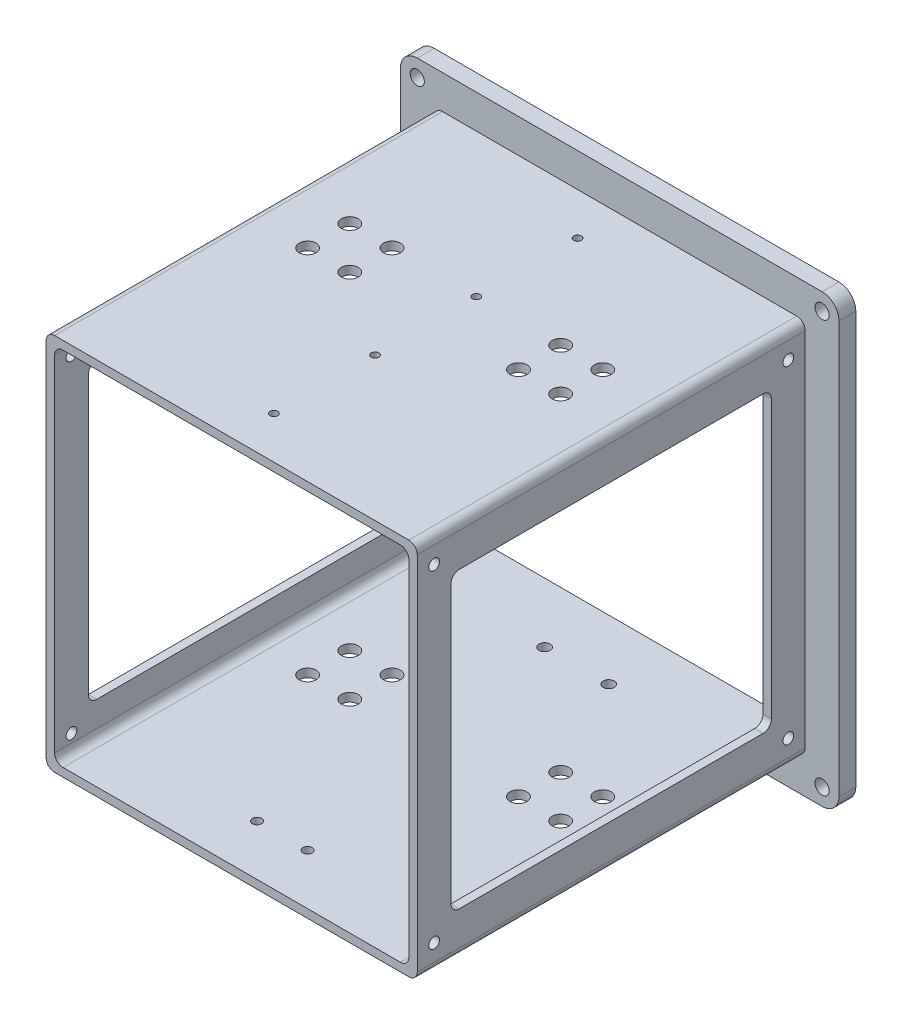
SolidWorks part; units mm, degrees
ref_plane "前视基准面" through (0, 0, 0) normal (0, 0, 1) x (1, 0, 0)
ref_plane "上视基准面" through (0, 0, 0) normal (0, 1, 0) x (1, 0, 0)
ref_plane "右视基准面" through (0, 0, 0) normal (1, 0, 0) x (0, 0, -1)
sketch "草图1" plane through (0, 0, 0) normal (0, 0, 1) x (1, 0, 0)
  line L1 (-105, -107.125) -> (105, -107.125)
  line L2 (-105, -107.125) -> (-105, 107.125)
  line L3 (-105, 107.125) -> (105, 107.125)
  line L4 (105, -107.125) -> (105, 107.125)
  line L5 (-105, -107.125) -> (105, 107.125) construction
  line L6 (-105, 107.125) -> (105, -107.125) construction
  line L7 (-110, -112.125) -> (110, -112.125)
  line L8 (-110, -112.125) -> (-110, 112.125)
  line L9 (-110, 112.125) -> (110, 112.125)
  line L10 (110, -112.125) -> (110, 112.125)
  line L11 (-110, -112.125) -> (110, 112.125) construction
  line L12 (-110, 112.125) -> (110, -112.125) construction
  point P0 (0, 0)
  point P6 (0, 0)
  dimension "D1" = 210
  dimension "D2" = 214.25
  dimension "D3" = 5
  dimension "D4" = 5
extrude "凸台-拉伸1" add sketch "草图1" along normal blind 230
sketch "草图2" plane through (0, 0, 0) normal (0, 0, -1) x (-1, 0, 0)
  line L0 (-110, 112.125) -> (110, 112.125) construction
  line L1 (-130, -132.125) -> (130, -132.125)
  line L2 (-130, -132.125) -> (-130, 132.125)
  line L3 (-130, 132.125) -> (130, 132.125)
  line L4 (130, -132.125) -> (130, 132.125)
  line L5 (-130, -132.125) -> (130, 132.125) construction
  line L6 (-130, 132.125) -> (130, -132.125) construction
  line L7 (-110, -112.125) -> (-110, 112.125) construction
  line L8 (105, 107.125) -> (105, -107.125) construction
  line L9 (105, -107.125) -> (-105, -107.125) construction
  line L10 (-105, -107.125) -> (-105, 107.125) construction
  line L11 (-105, 107.125) -> (105, 107.125) construction
  line L12 (105, 107.125) -> (105, -107.125)
  line L13 (105, -107.125) -> (-105, -107.125)
  line L14 (-105, -107.125) -> (-105, 107.125)
  line L15 (-105, 107.125) -> (105, 107.125)
  point P0 (0, 0)
  dimension "D1" = 20
  dimension "D2" = 20
extrude "凸台-拉伸2" add sketch "草图2" along normal blind 10
fillet "圆角1" radius 5 4 edges at (110, 112.125, 115) (110, -112.125, 115) (-110, -112.125, 115) (-110, 112.125, 115)
fillet "圆角2" radius 5 4 edges at (105, 107.125, 110) (-105, 107.125, 110) (105, -107.125, 110) (-105, -107.125, 110)
fillet "圆角3" radius 10 4 edges at (-130, 132.125, -5) (130, 132.125, -5) (130, -132.125, -5) (-130, -132.125, -5)
hole_wizard "Ø8.4 (8.4) 直径孔1" positions "草图3" profile "草图4" hole size "Ø8.4" standard "GB" end condition through all
sketch "草图3" plane through (0, 0, 0) normal (0, 0, 1) x (1, 0, 0)
  point P0 (120, 122.125)
  point P3 (120, -122.125)
  point P6 (-120, -122.125)
  point P10 (-120, 122.125)
sketch "草图4" plane through (120, 122.125, 0) normal (1, 0, 0) x (0, -1, 0)
  line L0 (0, 0) -> (0, 10)
  line L1 (0, 10) -> (4.2, 10)
  line L2 (4.2, 10) -> (4.2, 0)
  line L5 (4.2, 0) -> (0, 0)
  line L11 (0, -6.35) -> (0, 107.95) construction
  dimension "通孔孔直径" = 8.4
  dimension "通孔孔深度" = 10
sketch "草图18" plane through (0, 112.125, 0) normal (0, 1, 0) x (1, 0, 0)
  line L0 (105, -230) -> (-105, -230) construction
  line L1 (-105, 0) -> (-105, -230) construction
  line L2 (105, -230) -> (105, 0) construction
  point P0 (-75, -85)
  point P1 (-75, -110)
  point P2 (-50, -110)
  point P3 (-50, -85)
  point P5 (50, -110)
  point P6 (75, -110)
  point P8 (75, -85)
  point P16 (50, -85)
  dimension "D1" = 25
  dimension "D2" = 25
  dimension "D3" = 35.3553
  dimension "D4" = 25
  dimension "D5" = 35.3553
  dimension "D6" = 25
  dimension "D7" = 30
  dimension "D8" = 30
  dimension "D9" = 25
  dimension "D10" = 25
  dimension "D11" = 25
  dimension "D12" = 25
  dimension "D13" = 120
  dimension "D14" = 120
  dimension "D15" = 35.3553
  dimension "D16" = 55
hole_wizard "大小mm 暗销孔11" positions "草图33" profile "草图34" hole size "Ø10.0" standard "GB" end condition through all
sketch "草图33" plane through (0, 112.125, 0) normal (0, 1, 0) x (1, 0, 0)
  point P0 (-75, -85)
  point P3 (-50, -85)
  point P6 (-50, -110)
  point P9 (-75, -110)
  point P12 (50, -110)
  point P15 (50, -85)
  point P18 (75, -85)
  point P21 (75, -110)
sketch "草图34" plane through (-75, 112.125, 85) normal (1, 0, 0) x (0, 0, 1)
  line L0 (0, 0) -> (0, 244.25)
  line L1 (0, 244.25) -> (5, 244.25)
  line L2 (5, 244.25) -> (5, 0)
  line L5 (5, 0) -> (0, 0)
  line L11 (0, -6.35) -> (0, 107.95) construction
  dimension "通孔孔直径" = 10
  dimension "通孔孔深度" = 244.25
sketch "草图35" plane through (0, -112.125, 0) normal (0, -1, 0) x (1, 0, 0)
  line L0 (120, 0) -> (-120, 0) construction
  line L2 (-105, 0) -> (105, 0) construction
  line L3 (105, 0) -> (105, 230) construction
  line L4 (-105, 230) -> (-105, 0) construction
  point P0 (15, 200)
  point P1 (19, 25.5)
  point P2 (-19, 25.5)
  point P4 (-15, 200)
  dimension "D1" = 90
  dimension "D2" = 38
  dimension "D4" = 19
  dimension "D5" = 200
  dimension "D6" = 200
  dimension "D7" = 25.5
  dimension "D8" = 25.5
  dimension "D9" = 90
sketch "草图38" plane through (0, 112.125, 0) normal (0, 1, 0) x (1, 0, 0)
  line L0 (-105, 0) -> (-105, -230) construction
  line L2 (105, 0) -> (-105, 0) construction
  point P0 (0, -25)
  point P1 (0, -85)
  point P2 (0, -205)
  point P3 (0, -145)
  dimension "D1" = 105
  dimension "D2" = 60
  dimension "D3" = 60
  dimension "D4" = 60
  dimension "D5" = 25
  dimension "D6" = 105
  dimension "D7" = 105
  dimension "D8" = 105
hole_wizard "Ø4.5 (4.5) 直径孔1" positions "草图39" profile "草图40" hole size "Ø4.5" standard "GB" end condition up to next
sketch "草图39" plane through (0, 112.125, 0) normal (0, 1, 0) x (1, 0, 0)
  point P0 (0, -25)
  point P3 (0, -85)
  point P6 (0, -145)
  point P9 (0, -205)
sketch "草图40" plane through (0, 112.125, 25) normal (1, 0, 0) x (0, 0, 1)
  line L0 (0, 0) -> (0, 5)
  line L1 (0, 5) -> (2.25, 5)
  line L2 (2.25, 5) -> (2.25, 0)
  line L5 (2.25, 0) -> (0, 0)
  line L11 (0, -6.35) -> (0, 107.95) construction
  dimension "通孔孔直径" = 4.5
  dimension "通孔孔深度" = 5
hole_wizard "Ø6.6 (6.6) 直径孔1" positions "草图41" profile "草图42" hole size "Ø6.6" standard "GB" end condition up to next
sketch "草图41" plane through (0, -112.125, 0) normal (0, -1, 0) x (-1, 0, 0)
  point P0 (19, -25.5)
  point P3 (-19, -25.5)
sketch "草图42" plane through (-19, -112.125, 25.5) normal (1, 0, 0) x (0, 0, -1)
  line L0 (0, 0) -> (0, 5)
  line L1 (0, 5) -> (3.3, 5)
  line L2 (3.3, 5) -> (3.3, 0)
  line L5 (3.3, 0) -> (0, 0)
  line L11 (0, -6.35) -> (0, 107.95) construction
  dimension "通孔孔直径" = 6.6
  dimension "通孔孔深度" = 5
hole_wizard "Ø5.5 (5.5) 直径孔1" positions "草图43" profile "草图44" hole size "Ø5.5" standard "GB" end condition up to next
sketch "草图43" plane through (0, -112.125, 0) normal (0, -1, 0) x (-1, 0, 0)
  point P0 (15, -200)
  point P3 (-15, -200)
sketch "草图44" plane through (-15, -112.125, 200) normal (1, 0, 0) x (0, 0, -1)
  line L0 (0, 0) -> (0, 5)
  line L1 (0, 5) -> (2.75, 5)
  line L2 (2.75, 5) -> (2.75, 0)
  line L5 (2.75, 0) -> (0, 0)
  line L11 (0, -6.35) -> (0, 107.95) construction
  dimension "通孔孔直径" = 5.5
  dimension "通孔孔深度" = 5
sketch "草图45" plane through (-110, 0, 0) normal (-1, 0, 0) x (0, 0, 1)
  line L0 (230, 107.125) -> (0, 107.125) construction
  line L1 (210, -87.125) -> (20, -87.125)
  line L2 (210, -87.125) -> (210, 87.125)
  line L3 (210, 87.125) -> (20, 87.125)
  line L4 (20, -87.125) -> (20, 87.125)
  line L5 (210, -87.125) -> (20, 87.125) construction
  line L6 (210, 87.125) -> (20, -87.125) construction
  line L7 (0, -107.125) -> (230, -107.125) construction
  line L8 (0, -122.125) -> (0, 122.125) construction
  line L9 (230, 107.125) -> (230, -107.125) construction
  point P0 (115, 0)
  dimension "D1" = 20
  dimension "D2" = 20
  dimension "D3" = 20
  dimension "D4" = 20
extrude "切除-拉伸1" cut sketch "草图45" against normal through all
fillet "圆角4" radius 5 8 edges at (107.5, -87.125, 20) (107.5, -87.125, 210) (-107.5, -87.125, 210) (-107.5, -87.125, 20) (-107.5, 87.125, 210) (-107.5, 87.125, 20) (107.5, 87.125, 210) (107.5, 87.125, 20)
sketch "草图46" plane through (110, 0, 0) normal (1, 0, 0) x (0, 0, -1)
  line L0 (-205, 87.125) -> (-25, 87.125) construction
  line L1 (-210, -82.125) -> (-210, 82.125) construction
  line L2 (-20, 82.125) -> (-20, -82.125) construction
  line L3 (-25, -87.125) -> (-205, -87.125) construction
  point P0 (-220, 97.125)
  point P1 (-220, -97.125)
  point P2 (-10, -97.125)
  point P3 (-10, 97.125)
  dimension "D1" = 10
  dimension "D2" = 10
  dimension "D3" = 10
  dimension "D4" = 10
  dimension "D5" = 10
  dimension "D6" = 10
  dimension "D7" = 10
  dimension "D8" = 10
hole_wizard "Ø6.4 (6.4) 直径孔1" positions "草图47" profile "草图48" hole size "Ø6.4" standard "GB" end condition through all
sketch "草图47" plane through (110, 0, 0) normal (1, 0, 0) x (0, 0, -1)
  point P0 (-220, 97.125)
  point P3 (-10, 97.125)
  point P6 (-10, -97.125)
  point P9 (-220, -97.125)
sketch "草图48" plane through (110, 97.125, 220) normal (0, 1, 0) x (0, 0, -1)
  line L0 (0, 0) -> (0, 240)
  line L1 (0, 240) -> (3.2, 240)
  line L2 (3.2, 240) -> (3.2, 0)
  line L5 (3.2, 0) -> (0, 0)
  line L11 (0, -6.35) -> (0, 107.95) construction
  dimension "通孔孔直径" = 6.4
  dimension "通孔孔深度" = 240
